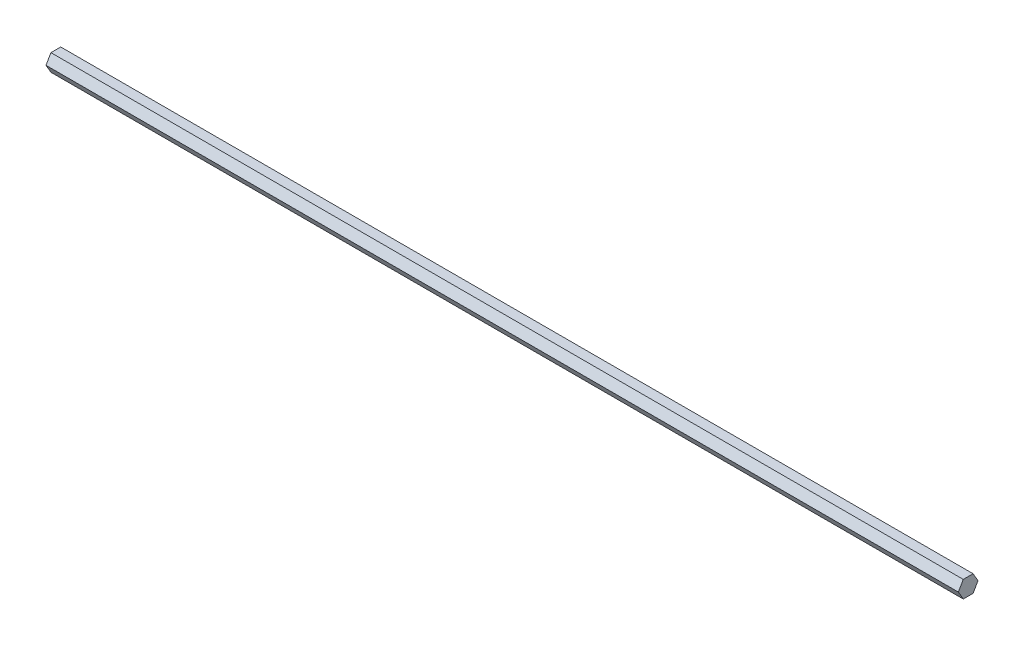
SolidWorks part; units mm, degrees
ref_plane "Front Plane" through (0, 0, 0) normal (0, 0, 1) x (1, 0, 0)
ref_plane "Top Plane" through (0, 0, 0) normal (0, 1, 0) x (1, 0, 0)
ref_plane "Right Plane" through (0, 0, 0) normal (1, 0, 0) x (0, 0, -1)
sketch "Sketch1" plane through (0, 0, 0) normal (1, 0, 0) x (0, 0, -1)
  line L1 (7.3323, 0) -> (3.6662, 6.35)
  line L2 (3.6662, 6.35) -> (-3.6662, 6.35)
  line L3 (-3.6662, 6.35) -> (-7.3323, 0)
  line L4 (-7.3323, 0) -> (-3.6662, -6.35)
  line L5 (-3.6662, -6.35) -> (3.6662, -6.35)
  line L6 (3.6662, -6.35) -> (7.3323, 0)
  circle A0 centre (0, 0) radius 6.35 construction
  dimension "D1" = 12.7
extrude "Boss-Extrude1" add sketch "Sketch1" along normal blind 680.847
